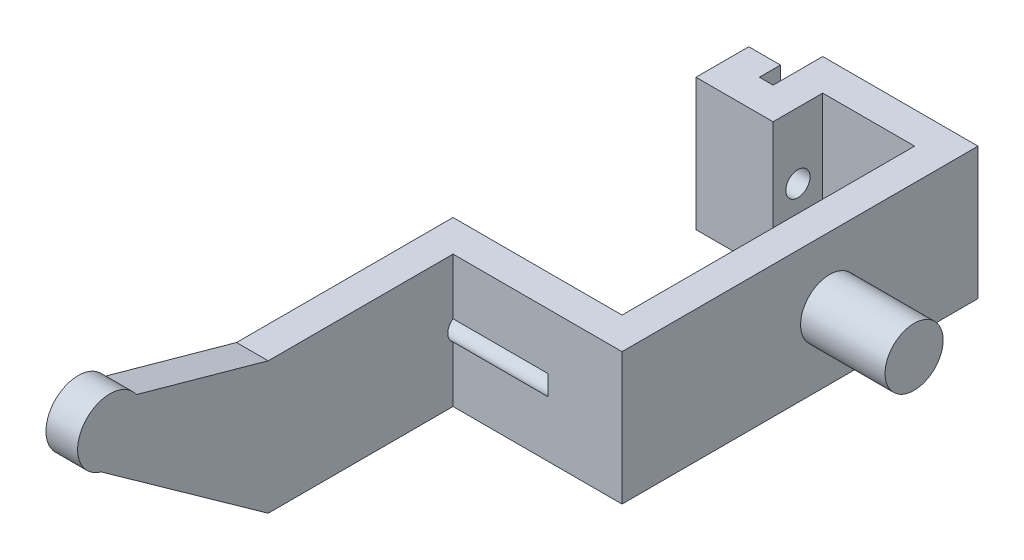
SolidWorks part; units mm, degrees
note: The reader was unsure of these and kept them because the rebuilt part matched: shared geometry of "草图4<8>".
ref_plane "前视基准面" through (0, 0, 0) normal (0, 0, 1) x (1, 0, 0)
ref_plane "上视基准面" through (0, 0, 0) normal (0, 1, 0) x (1, 0, 0)
ref_plane "右视基准面" through (0, 0, 0) normal (1, 0, 0) x (0, 0, -1)
sketch "草图1" plane through (0, 0, 0) normal (0, 1, 0) x (1, 0, 0)
  line L0 (0, 0) -> (16, 0)
  line L1 (16, 0) -> (16, -23)
  line L2 (16, -23) -> (0, -23)
  line L3 (0, -23) -> (0, -61)
  line L4 (0, 0) -> (0, 5)
  line L5 (0, 5) -> (3, 5)
  line L6 (3, 5) -> (3, 3)
  line L7 (3, 3) -> (4.3, 3)
  line L8 (19, 3) -> (19, -26)
  line L9 (19, -26) -> (3, -26)
  line L10 (3, -26) -> (3, -61)
  line L11 (3, -61) -> (0, -61)
  line L12 (16, 3) -> (16, 4.7)
  line L13 (16, 4.7) -> (7.3, 4.7)
  line L14 (7.3, 4.7) -> (7.3, 3)
  line L15 (4.3, 3) -> (4.3, 7.7)
  line L16 (4.3, 7.7) -> (19, 7.7)
  line L17 (19, 7.7) -> (19, 3)
  line L18 (7.3, 3) -> (7.3, 0)
  line L19 (16, 3) -> (16, 0)
  line L20 (7.3, 3) -> (16, 3)
  point P3 (8, 0)
  dimension "D1" = 3
  dimension "D2" = 3
  dimension "D3" = 3
  dimension "D4" = 3
  dimension "D5" = 16
  dimension "D6" = 3
  dimension "D7" = 23
  dimension "D8" = 5
  dimension "D9" = 35
  dimension "D10" = 1.7
  dimension "D11" = 8.7
  dimension "D12" = 3
  dimension "D13" = 3
  dimension "D14" = 3
extrude "凸台-拉伸1" add sketch "草图1" along normal blind 12.5 contours L12 L19 L1 L2 L3 L11 L10 L9 L8 L17 L16 L15 L7 L6 L5 L4 L0 L18 L14 L13
sketch "草图2" plane through (0, 0, 0) normal (-1, 0, 0) x (0, 0, 1)
  line L4 (23, 0) -> (61, 0)
  line L5 (61, 0) -> (61, 12.5)
  line L6 (23, 0) -> (61, 0)
  line L7 (23, 12.5) -> (23, 0)
  line L9 (61, 0) -> (61, 12.5)
  line L11 (23, 12.5) -> (23, 0)
  line L12 (-5, 0) -> (0, 0)
  line L13 (0, 0) -> (0, 12.5)
  line L14 (-5, 0) -> (0, 0)
  line L15 (-5, 12.5) -> (-5, 0)
  line L17 (0, 0) -> (0, 12.5)
  line L19 (-5, 12.5) -> (-5, 0)
  line L20 (61, 12.5) -> (23, 12.5)
  line L21 (61, 12.5) -> (23, 12.5)
  line L22 (0, 12.5) -> (-5, 12.5)
  line L23 (0, 12.5) -> (-5, 12.5)
  circle A0 centre (25.35, 6.25) radius 1.15
  circle A1 centre (-2.35, 6.25) radius 1.15
  dimension "D5" = 2.3
  dimension "D6" = 2.3
  dimension "D3" = 2.35
  dimension "D4" = 2.35
  dimension "D1" = 0
  dimension "D2" = 0
extrude "切除-拉伸1" cut sketch "草图2" against normal blind 12 contours A1 | A0
sketch "草图3" plane through (19, 0, 0) normal (1, 0, 0) x (0, 0, -1)
  line L0 (5, 12.5) -> (5, 0) construction
  line L4 (-26, 0) -> (7.7, 0)
  line L5 (-26, 0) -> (7.7, 0)
  line L6 (7.7, 0) -> (7.7, 12.5)
  line L7 (-26, 12.5) -> (-26, 0)
  line L11 (-26, 12.5) -> (-26, 0)
  line L13 (7.7, 0) -> (7.7, 12.5)
  line L14 (7.7, 12.5) -> (-26, 12.5)
  line L15 (7.7, 12.5) -> (-26, 12.5)
  circle A0 centre (-6.35, 6.25) radius 2.75
  dimension "D3" = 5.5
  dimension "D2" = 11.35
  dimension "D1" = 0
extrude "凸台-拉伸2" add sketch "草图3" along normal blind 8 contours A0
sketch "草图4" plane through (3, 0, 0) normal (1, 0, 0) x (0, 0, -1)
  line L0 (-52.25, 6.25) -> (-43.5, 12.5)
  line L3 (-43.5, 0) -> (-43.5, 12.5) construction
  line L4 (-52.25, 6.25) -> (-43.5, 6.25) construction
  line L5 (-26, 0) -> (-26, 5.3013)
  line L6 (-26, 7.1987) -> (-26, 12.5)
  line L7 (-26, 12.5) -> (-61, 12.5)
  line L8 (-61, 12.5) -> (-61, 0)
  line L9 (-26, 12.5) -> (-61, 12.5)
  line L10 (-26, 0) -> (-26, 5.3013)
  line L11 (-26, 7.1987) -> (-26, 12.5)
  line L13 (-61, 12.5) -> (-61, 0)
  line L15 (-61, 12.5) -> (-43.5, 0)
  line L16 (-43.5, 12.5) -> (-55.9744, 15.9683)
  line L22 (-61, 0) -> (-26, 0)
  line L23 (-61, 0) -> (-26, 0)
  arc A1 (-26, 7.1987) -> (-26, 5.3013) centre (-25.35, 6.25) ccw
  arc A2 (-26, 7.1987) -> (-26, 5.3013) centre (-25.35, 6.25) ccw
  circle A3 centre (-58.4872, 14.2341) radius 3.0531
  dimension "D1" = 0
extrude "凸台-拉伸3" add sketch "草图4" against normal blind 3
extrude "切除-拉伸5" cut sketch "草图4<8>" against normal blind 3
sketch "草图4<8>" plane through (3, 0, 0) normal (1, 0, 0) x (0, 0, -1) same geometry as "草图4"
